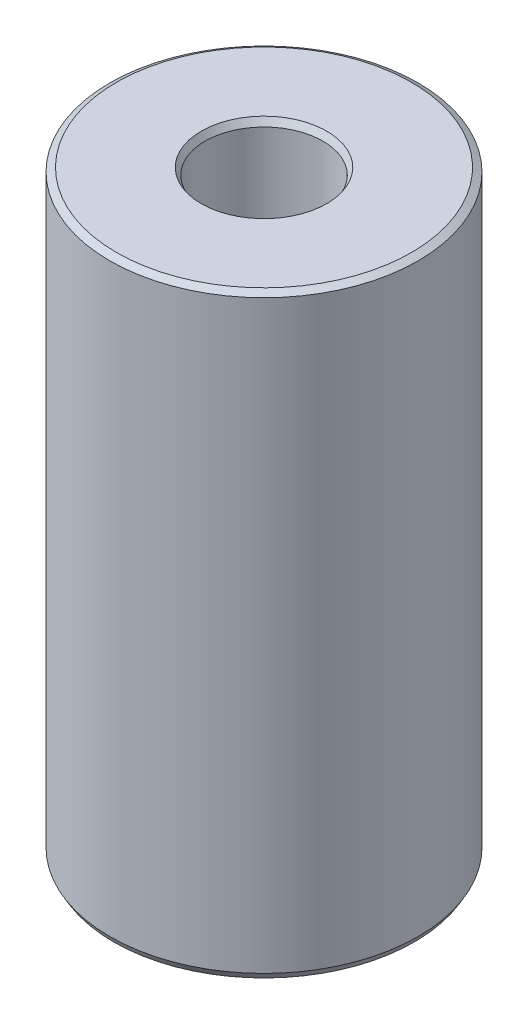
SolidWorks part; units mm, degrees
ref_plane "Front Plane" through (0, 0, 0) normal (0, 0, 1) x (1, 0, 0)
ref_plane "Top Plane" through (0, 0, 0) normal (0, 1, 0) x (1, 0, 0)
ref_plane "Right Plane" through (0, 0, 0) normal (1, 0, 0) x (0, 0, -1)
sketch "Sketch1" plane through (0, 0, 0) normal (0, 1, 0) x (1, 0, 0)
  circle A0 centre (0, 0) radius 10
  dimension "SLEEVE_OD" = 20
extrude "Boss-Extrude1" add sketch "Sketch1" along normal blind 38.6477
sketch "Sketch2" plane through (0, 0, 0) normal (0, 1, 0) x (1, 0, 0)
  circle A0 centre (0, 0) radius 3.8237
  dimension "BORE_D" = 7.6475
extrude "Cut-Extrude1" cut sketch "Sketch2" along normal through all
chamfer "Chamfer1" distance 0.25 angle 60 4 edges at (0, 38.6477, 3.8237) (0, 0, 3.8237) (0, 0, 10) (0, 38.6477, 10) first distance on face at (0, 38.6477, 3.8237) first distance on face at (0, 0, 3.8237) first distance on face at (0, 38.6477, 10)
